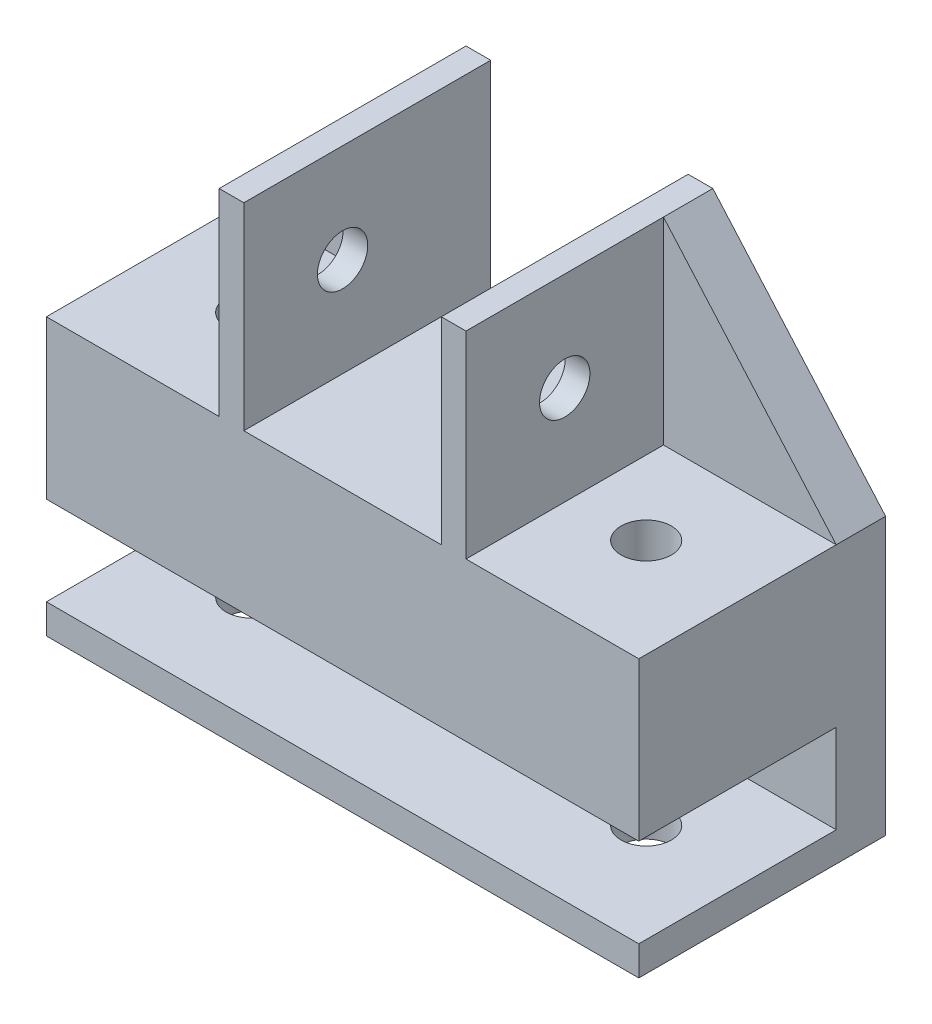
SolidWorks part; units mm, degrees
ref_plane "Front Plane" through (0, 0, 0) normal (0, 0, 1) x (1, 0, 0)
ref_plane "Top Plane" through (0, 0, 0) normal (0, 1, 0) x (1, 0, 0)
ref_plane "Right Plane" through (0, 0, 0) normal (1, 0, 0) x (0, 0, -1)
sketch "Sketch1" plane through (0, 0, 0) normal (0, 1, 0) x (1, 0, 0)
  line L0 (40, 0) -> (40, 25)
  line L1 (0, 0) -> (60, 0)
  line L2 (0, 0) -> (0, 25)
  line L3 (0, 25) -> (60, 25)
  line L4 (60, 0) -> (60, 25)
  line L5 (40, 0) -> (20, 0)
  line L6 (40, 25) -> (20, 25)
  line L7 (20, 0) -> (20, 25)
  line L8 (40, 0) -> (20, 25) construction
  line L9 (40, 25) -> (20, 0) construction
  point P5 (30, 10)
  point P6 (30, 12.5)
  dimension "D1" = 60
  dimension "D2" = 25
  dimension "D3" = 25
  dimension "D4" = 10
  dimension "D5" = 20
  dimension "D6" = 12.5
extrude "Boss-Extrude1" add sketch "Sketch1" along normal blind 20 contours L1 L7 L3 L2 | L1 L4 L3 L0 region at (50, 0, -12.5) region at (10, 0, -12.5)
extrude "Boss-Extrude2" add sketch "Sketch1<3>" against normal blind 28 contours L7 L1 L0 L3 | L1 L7 L3 L2 | L1 L4 L3 L0 region at (30, 0, -12.5) region at (50, 0, -12.5) region at (10, 0, -12.5)
sketch "Sketch1<3>" plane through (0, 0, 0) normal (0, 1, 0) x (1, 0, 0) same geometry as "Sketch1"
sketch "Sketch2" plane through (0, 0, 0) normal (0, 0, 1) x (1, 0, 0)
  line L0 (0, 20) -> (0, -28) construction
  line L1 (0, -25) -> (60, -25)
  line L2 (0, -25) -> (0, -16)
  line L3 (0, -16) -> (60, -16)
  line L4 (60, -25) -> (60, -16)
  line L5 (60, -28) -> (60, 20) construction
  dimension "D1" = 9
  dimension "D2" = 16
extrude "Cut-Extrude1" cut sketch "Sketch2" against normal blind 20
sketch "Sketch3" plane through (0, 0, 0) normal (0, 0, 1) x (1, 0, 0)
  line L0 (0, 0) -> (17.5, 20)
  line L1 (0, 20) -> (20, 20) construction
  line L2 (30, 0) -> (30, -16) construction
  line L3 (60, 0) -> (42.5, 20)
  line L10 (0, 20) -> (0, -16)
  line L11 (0, -16) -> (60, -16)
  line L12 (60, -16) -> (60, 20)
  line L13 (60, 20) -> (40, 20)
  line L16 (40, 20) -> (40, 0)
  line L17 (40, 20) -> (40, 0)
  line L18 (0, 20) -> (0, -16)
  line L19 (0, -16) -> (60, -16)
  line L20 (60, -16) -> (60, 20)
  line L21 (60, 20) -> (40, 20)
  line L26 (40, 0) -> (20, 0)
  line L27 (40, 0) -> (20, 0)
  line L28 (20, 0) -> (20, 20)
  line L29 (20, 0) -> (20, 20)
  line L30 (20, 20) -> (0, 20)
  line L31 (20, 20) -> (0, 20)
  line M11 (0, 20) -> (0, -16)
  line M13 (60, -16) -> (60, 20)
  line M14 (60, 20) -> (40, 20)
  line M18 (20, 20) -> (0, 20)
  dimension "D1" = 2.5
  dimension "D2" = 0
extrude "Cut-Extrude2" cut sketch "Sketch3" against normal through all contours L0 M11 M18 | L3 M13 M14 region at (5.8333, 13.3333, 0) region at (54.1667, 13.3333, 0)
sketch "Sketch4" plane through (60, 0, 0) normal (1, 0, 0) x (0, 0, -1)
  line L1 (5, 0) -> (20, 0)
  line L2 (5, 0) -> (5, 20)
  line L3 (5, 20) -> (20, 20)
  line L4 (0, 20) -> (0, 0)
  line L5 (0, 0) -> (25, 0)
  line L6 (25, 0) -> (25, 20)
  line L7 (25, 20) -> (0, 20)
  line L8 (0, 20) -> (0, 0)
  line L9 (0, 0) -> (25, 0)
  line L10 (25, 0) -> (25, 20)
  line L11 (25, 20) -> (0, 20)
  line L12 (20, 0) -> (20, 20)
  line M8 (25, 0) -> (0, 0)
  dimension "D2" = 5
  dimension "D3" = 5
  dimension "D1" = 0
extrude "Cut-Extrude3" cut sketch "Sketch4" against normal up to vertex (17.5 mm away) contours L12 L3 L2 M8 | L2 L11 L8 M8 region at (60, 10, -12.5) region at (60, 10, -2.5) up to point (42.5, 20, 0)
ref_plane "Plane1" through (30, 0, 0) normal (-1, 0, 0) x (0, 0, 1)
sketch "Sketch5" plane through (42.5, 0, 0) normal (1, 0, 0) x (0, 0, -1)
  line L0 (10, 20) -> (10, 0) construction
  line L4 (0, 0) -> (20, 0)
  line L5 (20, 0) -> (20, 20)
  line L6 (20, 20) -> (0, 20)
  line L7 (0, 20) -> (0, 0)
  line L8 (0, 0) -> (20, 0)
  line L9 (20, 0) -> (20, 20)
  line L10 (20, 20) -> (0, 20)
  line L13 (0, 20) -> (0, 0)
  circle A0 centre (10, 10) radius 2.55
  dimension "D2" = 5.1
  dimension "D1" = 0
extrude "Cut-Extrude5" cut sketch "Sketch5" against normal up to surface (2.5 mm away) contours L0 A0 | A0 L0 region at (42.5, 10, -11.0823) region at (42.5, 10, -8.9177) up to face at (40, 10, -12.5)
sketch "Sketch7" plane through (0, 0, 0) normal (0, 1, 0) x (1, 0, 0)
  line L4 (0, 0) -> (60, 0)
  line L5 (60, 0) -> (60, 20)
  line L6 (60, 20) -> (0, 20)
  line L7 (0, 20) -> (0, 0)
  line L8 (0, 0) -> (60, 0)
  line L9 (60, 0) -> (60, 20)
  line L10 (60, 20) -> (0, 20)
  line L11 (0, 20) -> (0, 0)
  circle A0 centre (50, 10.75) radius 2.55
  circle A1 centre (50, 10.75) radius 4.5
  dimension "D1" = 9
  dimension "D2" = 5.1
  dimension "D4" = 9.25
  dimension "D5" = 10
  dimension "D3" = 0
extrude "Cut-Extrude6" cut sketch "Sketch7" against normal through all and the other way through all contours A0 | A0 region at (50, 0, -10.75)
mirror "Mirror3" about plane through (30, 0, 0) normal (-1, 0, 0) of "Cut-Extrude5", "Cut-Extrude6", "Cut-Extrude3"
